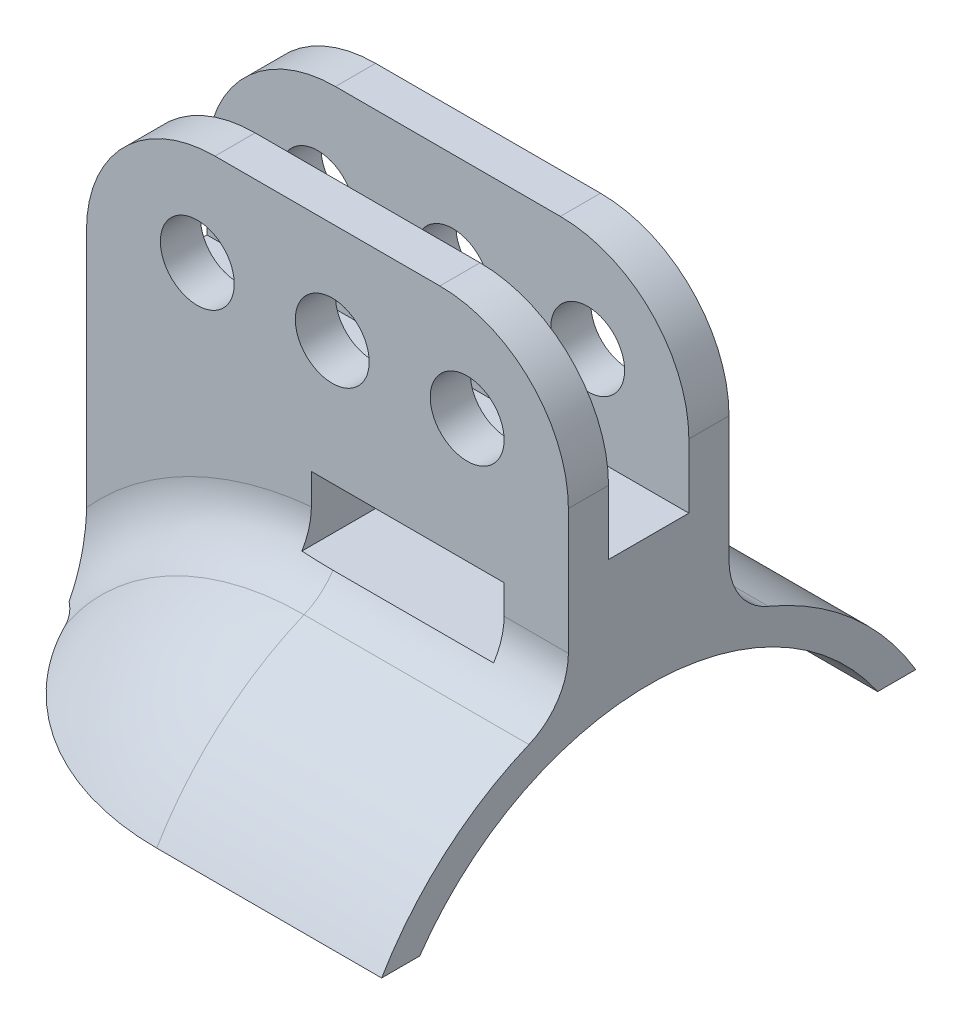
SolidWorks part; units mm, degrees
ref_plane "Front Plane" through (0, 0, 0) normal (0, 0, 1) x (1, 0, 0)
ref_plane "Top Plane" through (0, 0, 0) normal (0, 1, 0) x (1, 0, 0)
ref_plane "Right Plane" through (0, 0, 0) normal (1, 0, 0) x (0, 0, -1)
sketch "Sketch2" plane through (0, 0, 0) normal (1, 0, 0) x (0, 0, -1)
  circle A0 centre (0, 0) radius 10.9855
  circle A1 centre (0, 0) radius 12.2555
  dimension "D1" = 21.971
  dimension "D2" = 1.27
extrude "Boss-Extrude2" add sketch "Sketch2" along normal blind 15.24
sketch "Sketch3" plane through (0, 0, 0) normal (0, 1, 0) x (1, 0, 0)
  line L0 (0, 0) -> (-12.2555, 0)
  line L1 (0, 0) -> (0, 12.2555)
  circle A0 centre (0, 0) radius 12.2555
  circle A1 centre (0, 0) radius 10.9855
revolve "Revolve1" add sketch "Sketch3" angle 360 about L0 region at (-11.6205, 0, -0.1733)
sketch "Sketch4" plane through (0, 0, 0) normal (0, 1, 0) x (1, 0, 0)
  line L0 (15.24, -12.2555) -> (15.24, 12.2555) construction
  line L1 (15.24, 12.2555) -> (8.89, 12.2555)
  line L2 (15.24, 12.2555) -> (15.24, -12.2555)
  line L3 (15.24, -12.2555) -> (8.89, -12.2555)
  line L4 (8.89, 12.2555) -> (8.89, -12.2555)
  line L5 (0, 0) -> (15.24, 0) construction
  line L6 (15.24, 12.2555) -> (0, 12.2555) construction
  line L7 (0, -12.2555) -> (15.24, -12.2555) construction
  dimension "D3" = 6.35
extrude "Cut-Extrude1" cut sketch "Sketch4" against normal through all and the other way through all
ref_plane "Plane1" through (0, 12.2555, 0) normal (0, 1, 0) x (1, 0, 0)
sketch "Sketch6" plane through (0, 12.2555, 0) normal (0, 1, 0) x (1, 0, 0)
  line L0 (8.89, 3.175) -> (-10.16, 3.175)
  line L1 (8.89, 3.175) -> (8.89, -3.175)
  line L2 (-10.16, 3.175) -> (-10.16, -3.175)
  line L3 (8.89, -3.175) -> (-10.16, -3.175)
  line L5 (8.89, -12.2555) -> (8.89, 12.2555) construction
  point P6 (8.89, 0)
  point P7 (8.89, 0)
  dimension "D1" = 6.35
  dimension "D2" = 19.05
extrude "Boss-Extrude3" add sketch "Sketch6" along normal blind 11.43 and the other way up to surface other way up to face at (0, 0, -12.2555)
sketch "Sketch7" plane through (0, 0, 3.175) normal (0, 0, 1) x (1, 0, 0)
  line L1 (-10.16, 23.6855) -> (8.89, 23.6855) construction
  line L3 (8.89, 23.6855) -> (8.89, 11.8371) construction
  circle A0 centre (4.8895, 19.685) radius 1.4605
  point P5 (4.8895, 21.1455)
  point P8 (4.8895, 18.2245)
  point P9 (6.35, 19.685)
  dimension "D1" = 2.921
  dimension "D2" = 2.54
  dimension "D3" = 2.54
extrude "Cut-Extrude3" cut sketch "Sketch7" against normal through all
sketch "Sketch10" plane through (0, 12.2555, 0) normal (0, 1, 0) x (1, 0, 0)
  line L4 (0, -3.175) -> (0, 3.175)
  line L5 (-10.16, -3.175) -> (0, -3.175)
  line L6 (-10.16, 3.175) -> (-10.16, -3.175)
  line L7 (0, 3.175) -> (-10.16, 3.175)
  line L8 (0, -3.175) -> (0, 3.175)
  line L9 (-10.16, -3.175) -> (0, -3.175)
  line L10 (-10.16, 3.175) -> (-10.16, -3.175)
  line L11 (0, 3.175) -> (-10.16, 3.175)
  dimension "D1" = 0
extrude "Boss-Extrude5" add sketch "Sketch10" against normal up to surface (0.4184 mm away) up to face at (0, 0, 0)
sketch "Sketch8" plane through (8.89, 0, 0) normal (1, 0, 0) x (0, 0, -1)
  line L0 (-1.5875, 23.6855) -> (1.5875, 23.6855)
  line L1 (-1.5875, 23.6855) -> (-1.5875, 16.0655)
  line L2 (1.5875, 23.6855) -> (1.5875, 16.0655)
  line L3 (-1.5875, 16.0655) -> (1.5875, 16.0655)
  line L4 (-3.175, 23.6855) -> (3.175, 23.6855) construction
  point P6 (0, 23.6855)
  dimension "D1" = 7.62
  dimension "D2" = 3.175
pattern_linear "LPattern1" count 3 spacing 5.334 along (-1, 0, 0) of "Cut-Extrude3"
extrude "Cut-Extrude4" cut sketch "Sketch8" against normal through all
fillet "Fillet5" radius 5.08 4 edges at (-10.16, 23.6855, -2.3812) (8.89, 23.6855, -2.3813) (-10.16, 23.6855, 2.3813) (8.89, 23.6855, 2.3812)
fillet "Fillet6" radius 2.54 5 edges at (4.445, 11.8371, -3.175) (-5.8404, 10.2959, 3.175) (-10.16, 6.8536, 0) (-5.8404, 10.2959, -3.175) (4.445, 11.8371, 3.175)
sketch "Sketch11" plane through (8.89, 0, 0) normal (1, 0, 0) x (0, 0, -1)
  line L0 (-5.08, -9.7404) -> (5.08, -9.7404)
  circle A0 centre (0, 0) radius 10.9855 construction
  circle A1 centre (0, 0) radius 10.9855
  circle M1 centre (0, 0) radius 10.9855
  dimension "D1" = 10.16
extrude "Boss-Extrude6" add sketch "Sketch11" against normal up to surface (8.89 mm away) contours L0 M1 region at (8.89, -10.2409, 0) up to face at (0, 0, -10.9855)
sketch "Sketch13" plane through (0, 0, 3.175) normal (0, 0, 1) x (1, 0, 0)
  line L0 (-10.16, 16.0655) -> (8.89, 16.0655) construction
  line L1 (-10.16, 16.0655) -> (8.89, 16.0655)
  line L2 (8.89, 18.6055) -> (8.89, 13.6472) construction
  line L3 (-1.27, 14.7955) -> (6.35, 14.7955)
  line L4 (-1.27, 14.7955) -> (-1.27, 12.2555)
  line L5 (-1.27, 12.2555) -> (6.35, 12.2555)
  line L6 (6.35, 14.7955) -> (6.35, 12.2555)
  line L7 (-1.27, 14.7955) -> (6.35, 12.2555) construction
  line L8 (-1.27, 12.2555) -> (6.35, 14.7955) construction
  point P2 (2.54, 13.5255)
  arc M3 (-10.16, 9.1115) -> (0, 13.6472) centre (0, 0) cw
  line M4 (0, 13.6472) -> (8.89, 13.6472)
  dimension "D1" = 7.62
  dimension "D2" = 2.54
  dimension "D3" = 1.27
  dimension "D4" = 2.54
extrude "Cut-Extrude5" cut sketch "Sketch13" against normal through all and the other way through all contours L6 L3 L4 M3 M4 | L6 L4 L5 M4 M3 region at (2.53, 14.2197, 3.175) region at (2.5483, 12.9497, 3.175)
sketch "Sketch14" plane through (0, 0, 3.175) normal (0, 0, 1) x (1, 0, 0)
  line L0 (8.89, -12.2555) -> (8.89, 11.3043) construction
  line L1 (8.89, 6.2243) -> (-12.2555, 6.2243)
  line L2 (8.89, 6.2243) -> (8.89, -12.2555)
  line L3 (8.89, -12.2555) -> (-12.2555, -12.2555)
  line L4 (-12.2555, 6.2243) -> (-12.2555, -12.2555)
  line L5 (0, -12.2555) -> (8.89, -12.2555) construction
  arc A0 (-10.5197, 6.2875) -> (0, -12.2555) centre (0, 0) ccw construction
  dimension "D1" = 5.08
extrude "Cut-Extrude6" cut sketch "Sketch14" against normal through all and the other way through all
